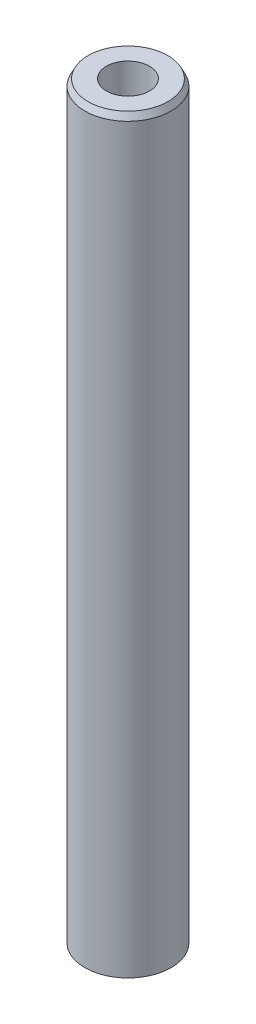
SolidWorks part; units mm, degrees
ref_plane "Front Plane" through (0, 0, 0) normal (0, 0, 1) x (1, 0, 0)
ref_plane "Top Plane" through (0, 0, 0) normal (0, 1, 0) x (1, 0, 0)
ref_plane "Right Plane" through (0, 0, 0) normal (1, 0, 0) x (0, 0, -1)
sketch "Sketch1" plane through (0, 0, 0) normal (0, 1, 0) x (1, 0, 0)
  circle A0 centre (0, 0) radius 32.5
  dimension "SHAFT_OD" = 65
extrude "Boss-Extrude1" add sketch "Sketch1" along normal blind 566.3558
sketch "Sketch2" plane through (0, 0, 0) normal (0, 1, 0) x (1, 0, 0)
  circle A0 centre (0, 0) radius 16.2275
  dimension "BORE_D" = 32.4551
extrude "Cut-Extrude1" cut sketch "Sketch2" along normal through all
chamfer "Chamfer1" distance 4.9088 angle 26.238 2 edges at (0, 566.3558, 32.5) (0, 0, 32.5) first distance on face at (0, 566.3558, 32.5) first distance on face at (0, 0, 16.2275)
